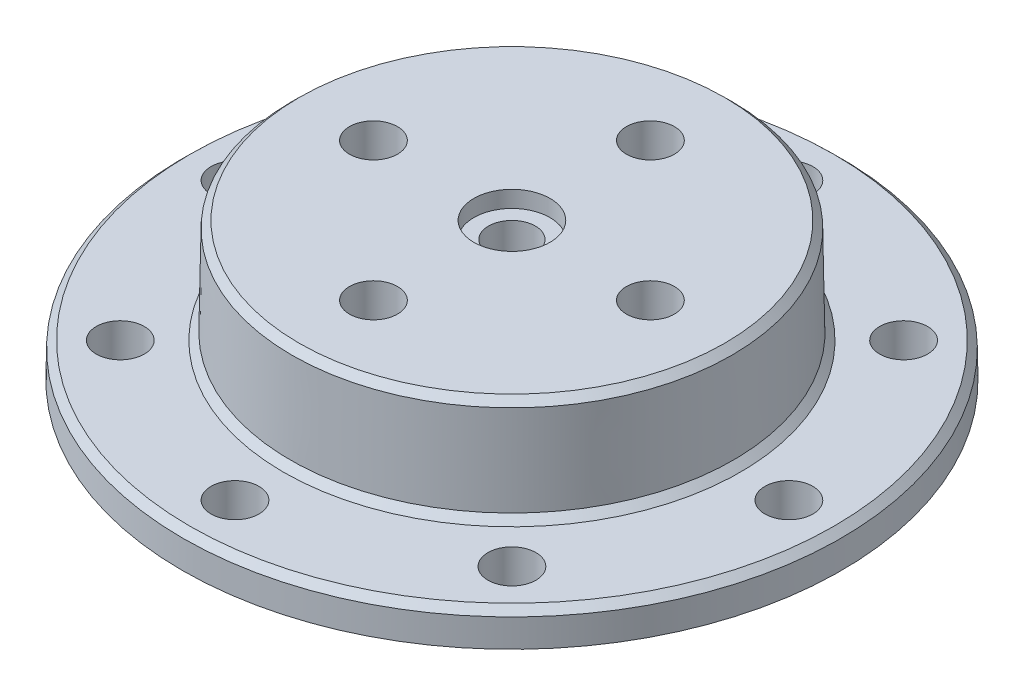
SolidWorks part; units mm, degrees
material "Nylon 101"
ref_plane "Front Plane" through (0, 0, 0) normal (0, 0, 1) x (1, 0, 0)
ref_plane "Top Plane" through (0, 0, 0) normal (0, 1, 0) x (1, 0, 0)
ref_plane "Right Plane" through (0, 0, 0) normal (1, 0, 0) x (0, 0, -1)
ref_plane "Plane1" through (0, 0, 0) normal (0, 0, -1) x (-1, 0, 0)
sketch "Sketch1" plane through (0, 0, 0) normal (0, 0, -1) x (-1, 0, 0)
  line L0 (-30.226, -3.175) -> (-18.82, -3.175)
  line L1 (-18.82, -3.175) -> (-18.7646, 0)
  line L2 (-18.7646, 0) -> (-30.1706, 0)
  line L3 (-30.1706, 0) -> (-30.226, -3.175)
  line L4 (0, -3.175) -> (0, 0) construction
revolve "Revolve1" add sketch "Sketch1" angle 360 about L4 reverse direction yes
sketch "Sketch2" plane through (0, 0, 0) normal (0, 1, 0) x (-1, 0, 0)
  circle A0 centre (0, 0) radius 20.32
extrude "Boss-Extrude1" add sketch "Sketch2" along normal blind 9.525 draft 1
sketch "Sketch3" plane through (0, -3.175, 0) normal (0, -1, 0) x (1, 0, 0)
  line L0 (-0.75, 20.3062) -> (-0.75, 21.7258)
  line L1 (-14.8321, 15.8928) -> (-13.8283, 14.8889)
  arc A0 (-13.8283, 14.8889) -> (-0.75, 20.3062) centre (0, 0) cw
  arc A1 (-0.75, 21.7258) -> (-1.8411, 28.6669) centre (0, 25.4) cw
  arc A2 (-1.8411, 28.6669) -> (-18.9687, 21.5724) centre (0, 0) ccw
  arc A3 (-18.9687, 21.5724) -> (-14.8321, 15.8928) centre (-17.9605, 17.9605) cw
extrude "Cut-Extrude1" cut sketch "Sketch3" against normal blind 1.675
sketch "Sketch4" plane through (0, -3.175, 0) normal (0, -1, 0) x (1, 0, 0)
  line L0 (0.75, 21.7258) -> (0.75, 20.3062)
  line L1 (13.8283, 14.8889) -> (14.8321, 15.8928)
  arc A0 (14.8321, 15.8928) -> (18.9687, 21.5724) centre (17.9605, 17.9605) cw
  arc A1 (18.9687, 21.5724) -> (1.8411, 28.6669) centre (0, 0) ccw
  arc A2 (1.8411, 28.6669) -> (0.75, 21.7258) centre (0, 25.4) cw
  arc A3 (0.75, 20.3062) -> (13.8283, 14.8889) centre (0, 0) cw
extrude "Cut-Extrude2" cut sketch "Sketch4" against normal blind 1.675
sketch "Sketch5" plane through (0, -3.175, 0) normal (0, -1, 0) x (1, 0, 0)
  line L0 (15.8928, 14.8321) -> (14.8889, 13.8283)
  line L1 (20.3062, 0.75) -> (21.7258, 0.75)
  arc A0 (28.6669, 1.8411) -> (21.5724, 18.9687) centre (0, 0) ccw
  arc A1 (21.5724, 18.9687) -> (15.8928, 14.8321) centre (17.9605, 17.9605) cw
  arc A2 (14.8889, 13.8283) -> (20.3062, 0.75) centre (0, 0) cw
  arc A3 (21.7258, 0.75) -> (28.6669, 1.8411) centre (25.4, 0) cw
extrude "Cut-Extrude3" cut sketch "Sketch5" against normal blind 1.675
sketch "Sketch6" plane through (0, -3.175, 0) normal (0, -1, 0) x (1, 0, 0)
  line L0 (21.7258, -0.75) -> (20.3062, -0.75)
  line L1 (14.8889, -13.8283) -> (15.8928, -14.8321)
  arc A0 (21.5724, -18.9687) -> (28.6669, -1.8411) centre (0, 0) ccw
  arc A1 (28.6669, -1.8411) -> (21.7258, -0.75) centre (25.4, 0) cw
  arc A2 (20.3062, -0.75) -> (14.8889, -13.8283) centre (0, 0) cw
  arc A3 (15.8928, -14.8321) -> (21.5724, -18.9687) centre (17.9605, -17.9605) cw
extrude "Cut-Extrude4" cut sketch "Sketch6" against normal blind 1.675
sketch "Sketch7" plane through (0, -3.175, 0) normal (0, -1, 0) x (1, 0, 0)
  line L0 (14.8321, -15.8928) -> (13.8283, -14.8889)
  line L1 (0.75, -20.3062) -> (0.75, -21.7258)
  arc A0 (1.8411, -28.6669) -> (18.9687, -21.5724) centre (0, 0) ccw
  arc A1 (18.9687, -21.5724) -> (14.8321, -15.8928) centre (17.9605, -17.9605) cw
  arc A2 (13.8283, -14.8889) -> (0.75, -20.3062) centre (0, 0) cw
  arc A3 (0.75, -21.7258) -> (1.8411, -28.6669) centre (0, -25.4) cw
extrude "Cut-Extrude5" cut sketch "Sketch7" against normal blind 1.675
sketch "Sketch8" plane through (0, -3.175, 0) normal (0, -1, 0) x (1, 0, 0)
  line L0 (-0.75, -21.7258) -> (-0.75, -20.3062)
  line L1 (-13.8283, -14.8889) -> (-14.8321, -15.8928)
  arc A0 (-14.8321, -15.8928) -> (-18.9687, -21.5724) centre (-17.9605, -17.9605) cw
  arc A1 (-18.9687, -21.5724) -> (-1.8411, -28.6669) centre (0, 0) ccw
  arc A2 (-1.8411, -28.6669) -> (-0.75, -21.7258) centre (0, -25.4) cw
  arc A3 (-0.75, -20.3062) -> (-13.8283, -14.8889) centre (0, 0) cw
extrude "Cut-Extrude6" cut sketch "Sketch8" against normal blind 1.675
sketch "Sketch9" plane through (0, -3.175, 0) normal (0, -1, 0) x (1, 0, 0)
  line L0 (-15.8928, -14.8321) -> (-14.8889, -13.8283)
  line L1 (-20.3062, -0.75) -> (-21.7258, -0.75)
  arc A0 (-21.7258, -0.75) -> (-28.6669, -1.8411) centre (-25.4, 0) cw
  arc A1 (-28.6669, -1.8411) -> (-21.5724, -18.9687) centre (0, 0) ccw
  arc A2 (-21.5724, -18.9687) -> (-15.8928, -14.8321) centre (-17.9605, -17.9605) cw
  arc A3 (-14.8889, -13.8283) -> (-20.3062, -0.75) centre (0, 0) cw
extrude "Cut-Extrude7" cut sketch "Sketch9" against normal blind 1.675
sketch "Sketch10" plane through (0, -3.175, 0) normal (0, -1, 0) x (1, 0, 0)
  line L0 (-21.7258, 0.75) -> (-20.3062, 0.75)
  line L1 (-14.8889, 13.8283) -> (-15.8928, 14.8321)
  arc A0 (-15.8928, 14.8321) -> (-21.5724, 18.9687) centre (-17.9605, 17.9605) cw
  arc A1 (-21.5724, 18.9687) -> (-28.6669, 1.8411) centre (0, 0) ccw
  arc A2 (-28.6669, 1.8411) -> (-21.7258, 0.75) centre (-25.4, 0) cw
  arc A3 (-20.3062, 0.75) -> (-14.8889, 13.8283) centre (0, 0) cw
extrude "Cut-Extrude8" cut sketch "Sketch10" against normal blind 1.675
sketch "Sketch11" plane through (0, 0, 0) normal (0, 0, 1) x (1, 0, 0)
  line L0 (4, 8.025) -> (0, 8.025)
  line L1 (0, 8.025) -> (0, 1.651)
  line L2 (0, 1.651) -> (4, 1.651)
  line L3 (4, 1.651) -> (4, 8.025)
  line L4 (0, 8.025) -> (0, 1.651) construction
revolve "Revolve2" add sketch "Sketch11" angle 360 about L4 reverse direction yes
hole_wizard "Ø4.4 (4.4) Diameter Hole1" positions "Sketch13" profile "Sketch12" hole size "Ø4.4" standard "ANSI Metric"
sketch "Sketch13" plane through (0, 0, 0) normal (0, 1, 0) x (1, 0, 0)
  point P0 (25.4, 0)
  point P1 (17.9605, 17.9605)
  point P2 (0, 25.4)
  point P3 (-17.9605, 17.9605)
  point P4 (-25.4, 0)
  point P5 (-17.9605, -17.9605)
  point P6 (0, -25.4)
  point P7 (17.9605, -17.9605)
sketch "Sketch12" plane through (25.4, 0, 0) normal (1, 0, 0) x (0, 0, 1)
  line L0 (0, 0) -> (0, 3.175)
  line L1 (0, 3.175) -> (2.2, 3.175)
  line L2 (2.2, 3.175) -> (2.2, 0)
  line L5 (2.2, 0) -> (0, 0)
  line L11 (0, -6.35) -> (0, 107.95) construction
  dimension "Thru Hole Dia." = 4.4
  dimension "Thru Hole Depth" = 3.175
hole_wizard "Ø4.4 (4.4) Diameter Hole2" positions "Sketch15" profile "Sketch14" hole size "Ø4.4" standard "ANSI Metric"
sketch "Sketch15" plane through (0, 9.525, 0) normal (0, 1, 0) x (1, 0, 0)
  point P0 (12.7, 0)
  point P1 (0, 12.7)
  point P2 (-12.7, 0)
  point P3 (0, -12.7)
sketch "Sketch14" plane through (12.7, 9.525, 0) normal (1, 0, 0) x (0, 0, 1)
  line L0 (0, 0) -> (0, 9.525)
  line L1 (0, 9.525) -> (2.2, 9.525)
  line L2 (2.2, 9.525) -> (2.2, 0)
  line L5 (2.2, 0) -> (0, 0)
  line L11 (0, -6.35) -> (0, 107.95) construction
  dimension "Thru Hole Dia." = 4.4
  dimension "Thru Hole Depth" = 9.525
hole_wizard "CBORE for M4 Hex Head Machine Screw1" positions "Sketch17" profile "Sketch16" counterbore size "M4" standard "ANSI Metric"
sketch "Sketch17" plane through (0, 9.525, 0) normal (0, 1, 0) x (1, 0, 0)
  point P0 (0, 0)
sketch "Sketch16" plane through (0, 9.525, 0) normal (1, 0, 0) x (0, 0, 1)
  line L0 (0, 0) -> (0, 9.525)
  line L1 (0, 9.525) -> (2.15, 9.525)
  line L3 (2.15, 9.525) -> (2.15, 1.524)
  line L4 (2.15, 1.524) -> (3.4925, 1.524)
  line L5 (3.4925, 1.524) -> (3.4925, 0)
  line L7 (3.4925, 0) -> (0, 0)
  line L11 (0, -6.35) -> (0, 107.95) construction
  dimension "Thru Hole Dia." = 4.3
  dimension "Thru Hole Depth" = 9.525
  dimension "C'Bore Dia." = 6.985
  dimension "C'Bore Depth" = 1.524
chamfer "Chamfer1" distance 0.635 angle 44.5 1 edges at (0, 0, 20.32) first distance on face at (25.4, 0, 2.2)
chamfer "Chamfer2" distance 0.635 angle 44.5 1 edges at (0, 9.525, 20.1537) first distance on face at (0, 9.525, 3.4925)
chamfer "Chamfer3" distance 0.635 angle 44.5 1 edges at (0, 0, 30.1706) first distance on face at (0, 0, 20.955)
